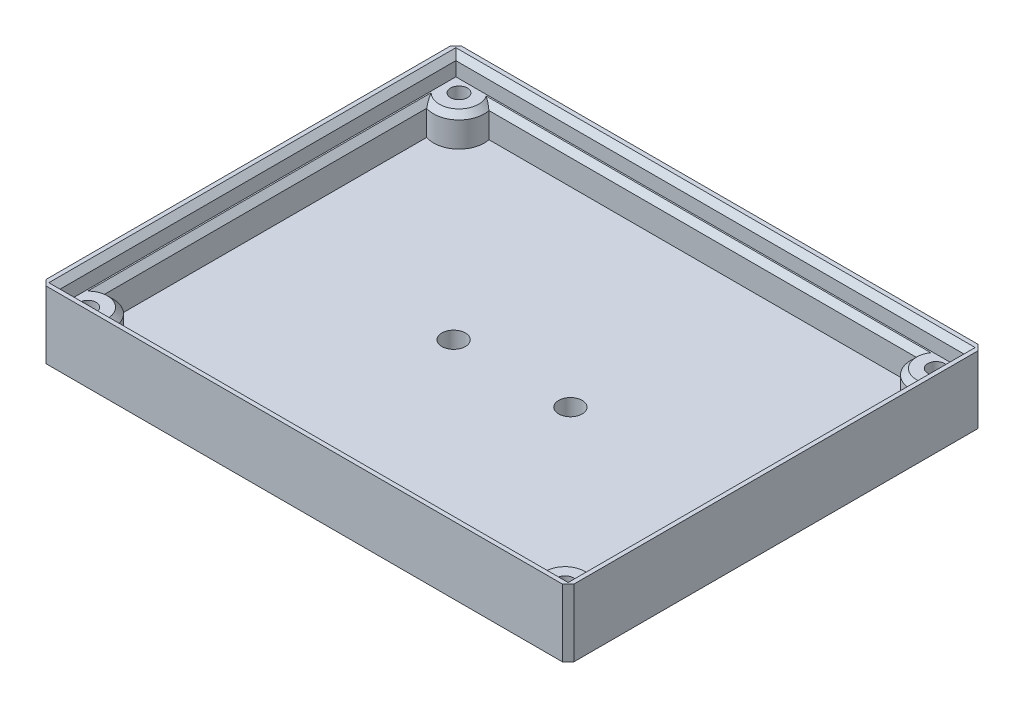
SolidWorks part; units mm, degrees
ref_plane "Front Plane" through (0, 0, 0) normal (0, 0, 1) x (1, 0, 0)
ref_plane "Top Plane" through (0, 0, 0) normal (0, 1, 0) x (1, 0, 0)
ref_plane "Right Plane" through (0, 0, 0) normal (1, 0, 0) x (0, 0, -1)
sketch "Sketch1" plane through (0, 0, 0) normal (0, 1, 0) x (1, 0, 0)
  line L0 (-47, -37) -> (-47, 37)
  line L1 (-45, -35) -> (45, -35) construction
  line L2 (-45, -35) -> (-45, 35) construction
  line L3 (-45, 35) -> (45, 35) construction
  line L4 (45, -35) -> (45, 35) construction
  line L5 (-45, -35) -> (45, 35) construction
  line L6 (-45, 35) -> (45, -35) construction
  line L7 (-47, 37) -> (47, 37)
  line L8 (47, -37) -> (47, 37)
  line L9 (-47, -37) -> (47, -37)
  point P0 (0, 0)
  dimension "D1" = 90
  dimension "D2" = 70
  dimension "D3" = 2
extrude "Boss-Extrude1" add sketch "Sketch1" along normal blind 12
sketch "Sketch2" plane through (0, 12, 0) normal (0, 1, 0) x (1, 0, 0)
  line L1 (-45.25, -35.25) -> (45.25, -35.25)
  line L2 (-45.25, -35.25) -> (-45.25, 35.25)
  line L3 (-45.25, 35.25) -> (45.25, 35.25)
  line L4 (45.25, -35.25) -> (45.25, 35.25)
  line L5 (-45.25, -35.25) -> (45.25, 35.25) construction
  line L6 (-45.25, 35.25) -> (45.25, -35.25) construction
  point P0 (0, 0)
  dimension "D1" = 90.5
  dimension "D2" = 70.5
extrude "Cut-Extrude1" cut sketch "Sketch2" against normal blind 3.5
sketch "Sketch3" plane through (0, 8.5, 0) normal (0, 1, 0) x (1, 0, 0)
  line L1 (45, -35) -> (-45, -35) construction
  line L2 (45, -35) -> (45, 35) construction
  line L3 (45, 35) -> (-45, 35) construction
  line L4 (-45, -35) -> (-45, 35) construction
  line L5 (45, -35) -> (-45, 35) construction
  line L6 (45, 35) -> (-45, -35) construction
  circle A0 centre (-42.5, 33.0556) radius 1.5
  circle A1 centre (42.5, 33.0556) radius 1.5
  circle A2 centre (42.5, -33.0556) radius 1.5
  circle A3 centre (-42.5, -33.0556) radius 1.5
  point P0 (0, 0)
  dimension "D4" = 3
  dimension "D1" = 90
  dimension "D2" = 70
  dimension "D3" = 2.5
extrude "Cut-Extrude2" cut sketch "Sketch3" against normal blind 6
shell "Shell1" thickness 3 removed face at (-42.5, 8.5, 34.5556)
chamfer "Chamfer1" distance 1 angle 45 4 edges at (45.25, 12, 0) (0, 12, 35.25) (-45.25, 12, 0) (0, 12, -35.25) tangent propagation no
chamfer "Chamfer2" distance 1 angle 45 8 edges at (0, 8.5, 34) (-39.5287, 8.5, 29.676) (-44, 8.5, 0) (39.5287, 8.5, 29.676) (44, 8.5, 0) (39.5287, 8.5, -29.676) (0, 8.5, -34) (-39.5287, 8.5, -29.676)
chamfer "Chamfer3" distance 1 angle 45 4 edges at (-47, 6, -37) (47, 6, -37) (47, 6, 37) (-47, 6, 37)
sketch "Sketch4" plane through (0, 3, 0) normal (0, 1, 0) x (1, 0, 0)
  circle A0 centre (-10.4, 0) radius 2.1
  circle A1 centre (10.4, 0) radius 2.1
  dimension "D3" = 4.2
  dimension "D1" = 10.4
  dimension "D2" = 10.4
extrude "Cut-Extrude3" cut sketch "Sketch4" against normal through all
